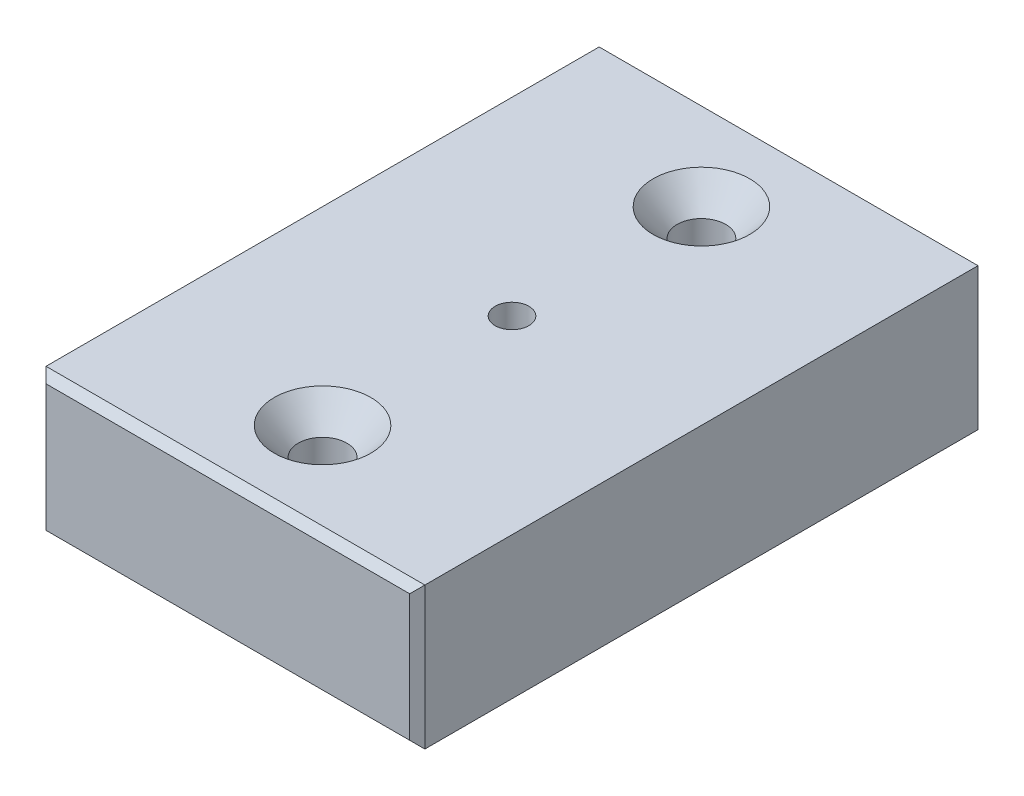
SolidWorks part; units mm, degrees
material "6061-T6 (SS)"
ref_plane "Front Plane" through (0, 0, 0) normal (0, 0, 1) x (1, 0, 0)
ref_plane "Top Plane" through (0, 0, 0) normal (0, 1, 0) x (1, 0, 0)
ref_plane "Right Plane" through (0, 0, 0) normal (1, 0, 0) x (0, 0, -1)
sketch "Sketch1" plane through (0, 0, 0) normal (0, 0, 1) x (1, 0, 0)
  line L1 (12.7, -4.7625) -> (-12.7, -4.7625)
  line L2 (12.7, -4.7625) -> (12.7, 4.7625)
  line L3 (12.7, 4.7625) -> (-12.7, 4.7625)
  line L4 (-12.7, -4.7625) -> (-12.7, 4.7625)
  line L5 (12.7, -4.7625) -> (-12.7, 4.7625) construction
  line L6 (12.7, 4.7625) -> (-12.7, -4.7625) construction
  point P0 (0, 0)
  dimension "D1" = 9.525
  dimension "D2" = 25.4
extrude "Boss-Extrude1" add sketch "Sketch1" along normal blind 38.1
hole_wizard "CSK for #4 Flat Head Socket Cap Screw1" positions "Sketch7" profile "Sketch8" countersink size "#4" standard "ANSI Inch" end condition up to next
sketch "Sketch7" plane through (0, 4.7625, 0) normal (0, 1, 0) x (1, 0, 0)
  line L1 (12.7, 0) -> (-12.7, 0) construction
  line L3 (0, -6.35) -> (0, 0)
  line L5 (0, -6.35) -> (0, -31.75)
  line L7 (0, -38.1) -> (0, -31.75)
  line L8 (12.7, -38.1) -> (-12.7, -38.1) construction
  point P7 (0, -6.35)
  point P15 (0, -31.75)
  dimension "D1" = 6.35
sketch "Sketch8" plane through (0, 4.7625, 6.35) normal (1, 0, 0) x (0, 0, 1)
  line L0 (0, 0) -> (0, 9.525)
  line L1 (0, 9.525) -> (1.6319, 9.525)
  line L2 (1.6319, 9.525) -> (1.6319, 1.8481)
  line L3 (1.6319, 1.8481) -> (3.2385, 0)
  line L5 (3.2385, 0) -> (0, 0)
  line L6 (-1.6319, 1.8481) -> (-3.2385, 0) construction
  line L11 (0, -6.35) -> (0, 107.95) construction
  dimension "Thru Hole Dia." = 3.2639
  dimension "Thru Hole Depth" = 9.525
  dimension "Near C'Sink Dia." = 6.477
  dimension "Near C'Sink Angle" = 82
hole_wizard "#4-40 Tapped Hole1" positions "Sketch9" profile "Sketch11" tap size "#4-40" standard "ANSI Inch" end condition up to next
sketch "Sketch9" plane through (0, 4.7625, 0) normal (0, 1, 0) x (1, 0, 0)
  line L0 (12.7, 0) -> (-12.7, 0) construction
  line L1 (-12.7, -38.1) -> (-12.7, 0) construction
  point P0 (0, -19.05)
  point P7 (0, 0)
  point P10 (-12.7, -19.05)
sketch "Sketch11" plane through (0, 4.7625, 19.05) normal (1, 0, 0) x (0, 0, 1)
  line L0 (0, 0) -> (0, 9.525)
  line L1 (0, 9.525) -> (1.1303, 9.525)
  line L2 (1.1303, 9.525) -> (1.1303, 0)
  line L5 (1.1303, 0) -> (0, 0)
  line L11 (0, -6.35) -> (0, 107.95) construction
  dimension "Thru Tap Drill Dia." = 2.2606
  dimension "Thru Tap Drill Depth" = 9.525
cosmetic thread "Hole Thread1" parameters "D2"=2.8448
chamfer "Chamfer1" distance 0.508 angle 45 8 edges at (0, 4.7625, 38.1) (12.7, 0, 38.1) (0, -4.7625, 38.1) (-12.7, 0, 38.1) (0, -4.7625, 0) (12.7, 0, 0) (0, 4.7625, 0) (-12.7, 0, 0)
